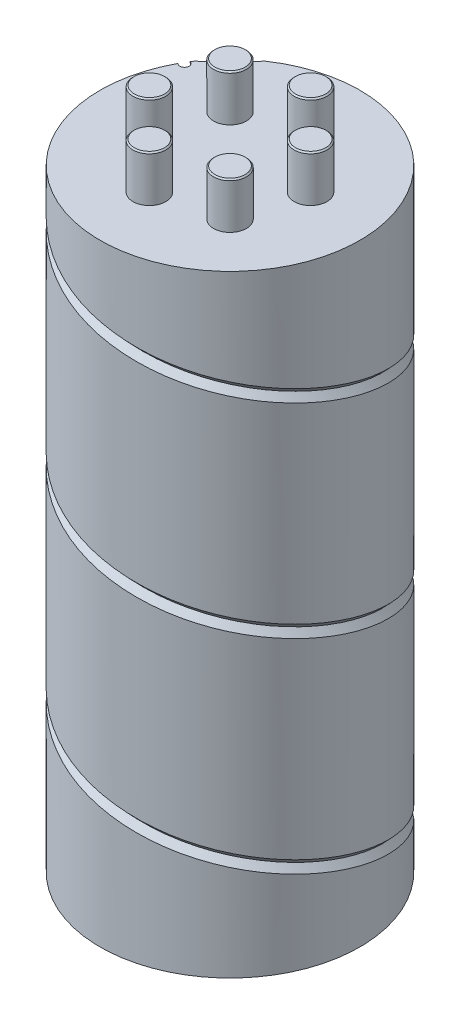
SolidWorks part; units mm, degrees
ref_plane "Front Plane" through (0, 0, 0) normal (0, 0, 1) x (1, 0, 0)
ref_plane "Top Plane" through (0, 0, 0) normal (0, 1, 0) x (1, 0, 0)
ref_plane "Right Plane" through (0, 0, 0) normal (1, 0, 0) x (0, 0, -1)
sketch "Sketch1" plane through (0, 0, 0) normal (0, 1, 0) x (1, 0, 0)
  line L0 (-19.75, 0) -> (19.75, 0) construction
  circle A0 centre (0, 0) radius 19.75
  dimension "D1" = 39.5
curve "Helix - Antenna Guide" pitch 31 height 93 radius 19.75 left hand yes centre (0, 0, 0) axis (0, 1, 0) start towards (0, 0, 1)
extrude "Extrude - Main Body" add sketch "Sketch1<2>" along normal blind 93
sketch "Sketch1<2>" plane through (0, 0, 0) normal (0, 1, 0) x (1, 0, 0) same geometry as "Sketch1"
ref_point "Point2"
ref_point "Point1"
ref_plane "Plane1" through (-13.9654, 0, -13.9654) normal (0.686, 0.2424, -0.686) x (-0.7276, 0.2285, -0.6468)
sketch "Sketch2" plane through (0, 93, 0) normal (0, 1, 0) x (1, 0, 0)
  line L0 (-19.077, -5.1117) -> (19.077, 5.1117) construction
  line L1 (5.1117, 19.077) -> (-5.1117, -19.077) construction
  line L2 (13.9654, -13.9654) -> (-13.9654, 13.9654) construction
  circle A1 centre (0, 0) radius 10 construction
  circle A2 centre (-9.6593, -2.5882) radius 2.5
  circle A3 centre (-7.0711, 7.0711) radius 2.5
  circle A4 centre (2.5882, 9.6593) radius 2.5
  circle A5 centre (9.6593, 2.5882) radius 2.5
  circle A6 centre (7.0711, -7.0711) radius 2.5
  circle A7 centre (-2.5882, -9.6593) radius 2.5
  circle A8 centre (0, 0) radius 19.75 construction
  point P2 (0, 0)
  point P4 (0, 0)
  point P9 (-19.6001, -2.4288)
  point P24 (0, 0)
  point P25 (0, 0)
  point P26 (0, 0)
  point P27 (0, 0)
  point P28 (0, 0)
  point P29 (0, 0)
  point P30 (-13.8542, 14.0757)
  point P31 (0, 0)
  point P32 (-10, 17.0312)
  point P33 (0, 0)
  point P34 (0, 0)
  point P35 (0, 0)
  point P36 (0, 0)
  point P37 (0, 0)
  point P38 (0, 0)
  point P39 (0, 0)
  point P40 (0, 0)
  point P41 (0, 0)
  point P42 (0, 0)
  point P43 (0, 0)
  point P44 (0, 0)
  point P45 (0, 0)
  point P46 (0, 0)
  point P47 (0, 0)
  point P48 (0, 0)
  point P49 (0, 0)
  point P50 (0, 0)
  point P51 (0, 0)
  point P52 (0, 0)
  point P54 (0, 0)
  point P55 (0, 0)
  point P56 (0, 0)
  point P57 (0, 0)
  point P58 (0, 0)
  point P59 (0, 0)
  point P60 (-19.75, 0)
  point P61 (-19.75, 0)
  point P62 (0, 0)
  point P63 (-19.75, 0)
  point P64 (-19.2698, -4.3284)
  point P66 (-19.75, 0)
  point P67 (-19.0175, -5.329)
  point P68 (0, 0)
  point P69 (-19.7444, 0.4698)
  point P72 (-10, 17.0312)
  point P73 (0, 0)
  point P74 (-13.4244, 14.4861)
  point P75 (0, 0)
  point P76 (-11.4639, 16.0823)
  dimension "D3" = 20
  dimension "D4" = 5
  dimension "D5" = 5
  dimension "D6" = 5
  dimension "D7" = 5
  dimension "D8" = 5
  dimension "D9" = 5
  dimension "D1" = 60
  dimension "D2" = 60
extrude "Extrude - Top Pegs" add sketch "Sketch2" along normal blind 7
sketch "Sketch15" plane through (-13.9654, 0, -13.9654) normal (0.686, 0.2424, -0.686) x (-0.7276, 0.2285, -0.6468)
  line L4 (0, 0) -> (0.2165, 0.8934)
  line L5 (0.2165, 0.8934) -> (-0.8934, 0.2165)
  line L8 (0, 0) -> (-0.2165, -0.8934)
  line L9 (-0.2165, -0.8934) -> (-0.8934, 0.2165)
  point P4 (0, 0)
  point P10 (-0.3384, 0.5549)
  point P11 (0, 0)
  dimension "D1" = 0.65
  dimension "D2" = 90
sweep "Cut - Antenna Wire Guide" cut profiles "Sketch15" path "Helix - Antenna Guide" align with end faces yes
ref_axis "Axis2" through (-2.5882, 100, 9.6593) along (0, -1, 0)
ref_axis "Axis3" through (7.0711, 100, 7.0711) along (0, -1, 0)
ref_axis "Axis4" through (9.6593, 100, -2.5882) along (0, -1, 0)
ref_axis "Axis5" through (2.5882, 100, -9.6593) along (0, -1, 0)
ref_axis "Axis6" through (-7.0711, 100, -7.0711) along (0, -1, 0)
ref_axis "Axis7" through (-9.6593, 100, 2.5882) along (0, -1, 0)
sketch "Sketch18" plane through (0, 0, 0) normal (0, -1, 0) x (1, 0, 0)
  circle A0 centre (-2.5882, 9.6593) radius 2.55
  circle A1 centre (7.0711, 7.0711) radius 2.55
  circle A2 centre (9.6593, -2.5882) radius 2.55
  circle A3 centre (2.5882, -9.6593) radius 2.55
  circle A4 centre (-7.0711, -7.0711) radius 2.55
  circle A5 centre (-9.6593, 2.5882) radius 2.55
  point P13 (0, 0)
  point P17 (0, 0)
  point P18 (0, 0)
  point P20 (0, 0)
  point P22 (0, 0)
  dimension "D1" = 5.1
  dimension "D2" = 5.1
  dimension "D3" = 5.1
  dimension "D4" = 5.1
  dimension "D5" = 5.1
  dimension "D6" = 5.1
extrude "Cut - Peg Holes" cut sketch "Sketch18" against normal blind 8
ref_plane "Plane2" through (0, 8, 0) normal (0, -1, 0) x (-1, 0, 0)
sketch "Sketch19" plane through (0, 8, 0) normal (0, -1, 0) x (-1, 0, 0)
  circle A0 centre (2.5882, -9.6593) radius 2.55
  circle A1 centre (-9.6593, 2.5882) radius 2.55
  circle A2 centre (-2.5882, 9.6593) radius 2.55
  circle A3 centre (7.0711, 7.0711) radius 2.55
  circle A4 centre (9.6593, -2.5882) radius 2.5882
  circle A5 centre (-7.0711, -7.0711) radius 2.55
extrude "Cut - Peg Hole Cones" cut sketch "Sketch19" against normal blind 8 draft 35
sketch "Sketch20" plane through (0, 93, 0) normal (0, 1, 0) x (1, 0, 0)
  line L0 (17.0132, -10.0306) -> (-17.0132, 10.0306) construction
  circle A0 centre (-16.841, 9.929) radius 0.7
  arc A1 (-16.3699, 11.0494) -> (-11.0494, 16.3699) centre (0, 0) ccw construction
  circle A2 centre (7.0711, -7.0711) radius 2.5 construction
  circle A3 centre (-7.0711, 7.0711) radius 2.5 construction
  point P11 (0, 0)
  dimension "D1" = 1.4
  dimension "D2" = 0.2
extrude "Cut - Wire Top Hole" cut sketch "Sketch20" against normal up to next
sketch "Sketch21" plane through (0, 93, 0) normal (0, 1, 0) x (1, 0, 0)
  circle A0 centre (-15.706, 6.9591) radius 1
  point P2 (-15.607, 8.5009)
  point P3 (-15.1144, 8.5209)
  point P4 (-16.0968, 6.7297)
  point P5 (-15.706, 6.9591)
  dimension "D1" = 2
extrude "Extrude - Wire Top Anchor Peg" [suppressed] add sketch "Sketch21" along normal blind 2 draft 20 draft outward yes
sketch "Sketch22" plane through (0, 0, 0) normal (0, -1, 0) x (1, 0, 0)
  line L0 (9.9425, 17.0648) -> (-9.9425, -17.0648) construction
  arc A0 (-11.0473, -16.3713) -> (-16.3713, -11.0473) centre (0, 0) ccw construction
  circle A1 centre (7.0711, 7.0711) radius 2.55 construction
  circle A2 centre (-7.0711, -7.0711) radius 2.55 construction
  circle A3 centre (-9.8418, -16.892) radius 0.7
  point P12 (0, 0)
  dimension "D1" = 0.2
  dimension "D2" = 1.4
extrude "Cut - Wire to Board Hole" cut sketch "Sketch22" against normal up to next
ref_axis "Ancher Peg Centerline" [suppressed] through (-15.706, 95, -6.9591) along (0, -1, 0)
sketch "Sketch23" [suppressed] plane through (0, 0, 0) normal (0, -1, 0) x (1, 0, 0)
  circle A0 centre (-15.706, -6.9591) radius 1.75
  point P2 (0, 0)
  dimension "D1" = 3.5
extrude "Cut - Anchor Peg Hole" [suppressed] cut sketch "Sketch23" against normal blind 2
sketch "Sketch24" [suppressed] plane through (0, 2, 0) normal (0, -1, 0) x (1, 0, 0)
  circle A0 centre (-15.706, -6.9591) radius 1.75
extrude "Cut - Ancher Peg Hole Cone" [suppressed] cut sketch "Sketch24" against normal blind 2 draft 40
chamfer "Chamfer1" [suppressed] distance 0.2 angle 45
chamfer "Chamfer2" distance 0.2 angle 45 6 edges at (-9.6593, 100, 5.0882) (-2.5882, 100, 12.1593) (7.0711, 100, 9.5711) (9.6593, 100, -0.0882) (2.5882, 100, -7.1593) (-7.0711, 100, -4.5711)
equation "\"pegD\"=5"
equation "\"D4@Sketch2\"=\"pegD\""
equation "\"D5@Sketch2\"=\"pegD\""
equation "\"D6@Sketch2\"=\"pegD\""
equation "\"D7@Sketch2\"=\"pegD\""
equation "\"D8@Sketch2\"=\"pegD\""
equation "\"D9@Sketch2\"=\"pegD\""
equation "\"pegHoleD\"=5.1"
equation "\"D1@Sketch18\"=\"pegHoleD\""
equation "\"D2@Sketch18\"=\"pegHoleD\""
equation "\"D3@Sketch18\"=\"pegHoleD\""
equation "\"D4@Sketch18\"=\"pegHoleD\""
equation "\"D5@Sketch18\"=\"pegHoleD\""
equation "\"D6@Sketch18\"=\"pegHoleD\""
